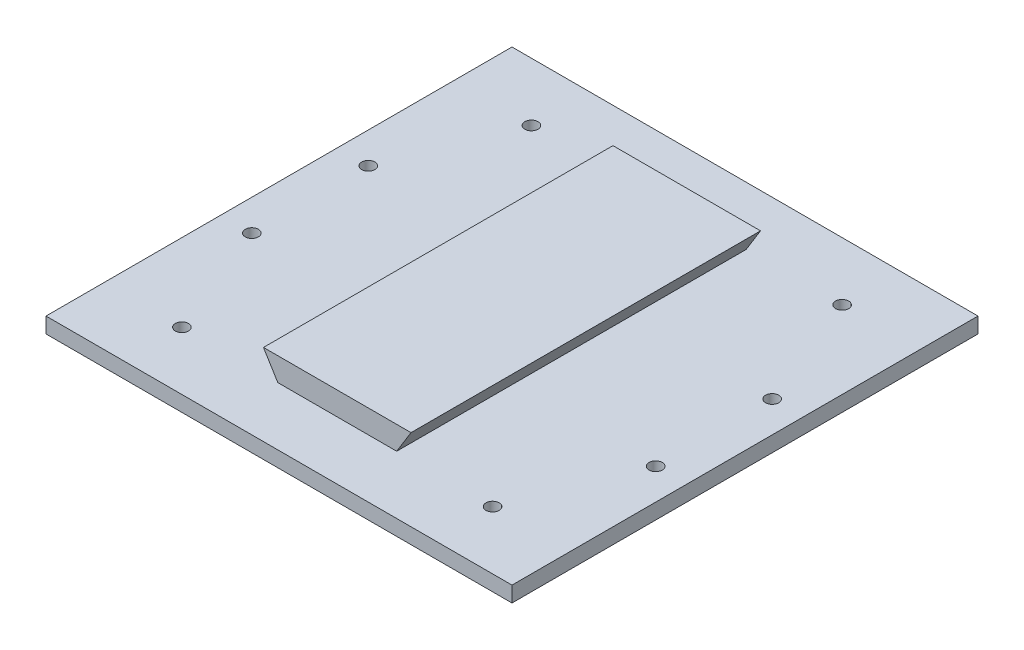
SolidWorks part; units mm, degrees
ref_plane "Front Plane" through (0, 0, 0) normal (0, 0, 1) x (1, 0, 0)
ref_plane "Top Plane" through (0, 0, 0) normal (0, 1, 0) x (1, 0, 0)
ref_plane "Right Plane" through (0, 0, 0) normal (1, 0, 0) x (0, 0, -1)
sketch "Sketch1" plane through (0, 0, 0) normal (0, 1, 0) x (1, 0, 0)
  line L1 (-60, -60) -> (60, -60)
  line L2 (-60, -60) -> (-60, 60)
  line L3 (-60, 60) -> (60, 60)
  line L4 (60, -60) -> (60, 60)
extrude "Rail Plate" add sketch "Sketch1" along normal blind 4
sketch "Sketch2" plane through (0, 0, 0) normal (0, 0, 1) x (1, 0, 0)
  line L0 (-15, 3.5) -> (15, 3.5)
  line L1 (15, 3.5) -> (19, 10)
  line L2 (19, 10) -> (-19, 10)
  line L3 (-19, 10) -> (-15, 3.5)
extrude "Dovetail Rail" add sketch "Sketch2" along normal mid plane 90
sketch "Sketch3" plane through (0, 0, 0) normal (0, 1, 0) x (1, 0, 0)
  circle A0 centre (-40, -45) radius 1.7
  circle A1 centre (-40, 45) radius 1.7
  circle A2 centre (40, -45) radius 1.7
  circle A3 centre (40, 45) radius 1.7
  circle A4 centre (-52, -15) radius 1.7
  circle A5 centre (-52, 15) radius 1.7
  circle A6 centre (52, -15) radius 1.7
  circle A7 centre (52, 15) radius 1.7
extrude "Bolt Holes" cut sketch "Sketch3" against normal through all and the other way through all
equation "\"PlateS\" = 120.0"
equation "\"PlateT\" = 4.0"
equation "\"RailW\" = 30.0"
equation "\"RailW2\" = 38.0"
equation "\"RailH\" = 6.0"
equation "\"RailL\" = 90.0"
equation "\"JoinL\" = 44.0"
equation "\"JoinW\" = 20.0"
equation "\"JoinT\" = 3.0"
equation "\"JoinPitch\" = 24.0"
equation "\"BoltD\" = 3.4"
